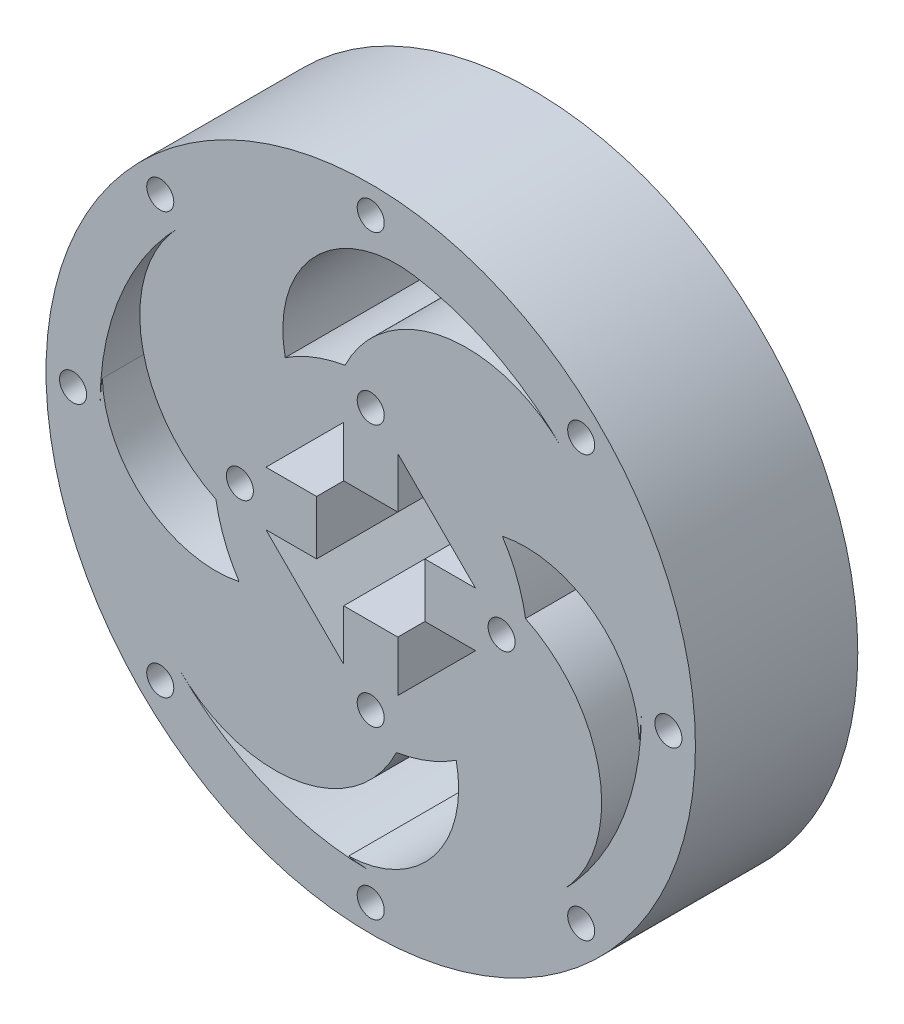
SolidWorks part; units mm, degrees
ref_plane "Front Plane" through (0, 0, 0) normal (0, 0, 1) x (1, 0, 0)
ref_plane "Top Plane" through (0, 0, 0) normal (0, 1, 0) x (1, 0, 0)
ref_plane "Right Plane" through (0, 0, 0) normal (1, 0, 0) x (0, 0, -1)
sketch "Sketch6" plane through (0, 0, 0) normal (0, 0, 1) x (1, 0, 0)
  circle A0 centre (0, 0) radius 20
  circle A1 centre (0, 0) radius 29
  dimension "D1" = 40
  dimension "D2" = 58
extrude "Inner Ring" add sketch "Sketch6" against normal blind 30 separate body
sketch "Sketch7" plane through (0, 0, 0) normal (0, 0, 1) x (1, 0, 0)
  line L2 (-10, 5) -> (-10, -5)
  line L3 (-5, 10) -> (5, 10)
  line L4 (10, 5) -> (10, -5)
  line L5 (-5, -10) -> (5, -10)
  line L14 (-19.3649, 5) -> (-10, 5)
  line L15 (-19.3649, -5) -> (-10, -5)
  line L16 (-5, 19.3649) -> (-5, 10)
  line L17 (5, 19.3649) -> (5, 10)
  line L18 (19.3649, 5) -> (10, 5)
  line L19 (19.3649, -5) -> (10, -5)
  line L20 (5, -19.3649) -> (5, -10)
  line L21 (-5, -19.3649) -> (-5, -10)
  circle A1 centre (0, 0) radius 20
  circle M19 centre (0, 0) radius 20
  dimension "D1" = 20
  dimension "D2" = 20
  dimension "D3" = 10
  dimension "D5" = 10
  dimension "D7" = 10
  dimension "D8" = 10
extrude "Motor Connector Cut" add sketch "Sketch7" against normal blind 30 contours L19 L18 L4 M19 | L17 L16 L3 M19 | L15 L2 L14 M19 | L21 L20 L5 M19 region at (-14.8967, 0, 0) region at (0, 14.8967, 0) region at (0, -14.8967, 0) region at (14.8967, 0, 0)
sketch "Sketch8" plane through (0, 0, 0) normal (0, 0, 1) x (1, 0, 0)
  circle A1 centre (0, 24.1825) radius 2.5
  circle A2 centre (24.1825, 0) radius 2.5
  circle A3 centre (0, -24.1825) radius 2.5
  circle A4 centre (-24.1825, 0) radius 2.5
  dimension "D1" = 5
  dimension "D2" = 5
  dimension "D3" = 5
  dimension "D4" = 5
  dimension "D6" = 48.3649
  dimension "D8" = 48.3649
extrude "M3 Holes" cut sketch "Sketch8" against normal blind 100 and the other way blind 38
sketch "Sketch9" plane through (0, 0, 0) normal (0, 0, 1) x (1, 0, 0)
  circle A0 centre (0, 0) radius 50
  circle A1 centre (0, 0) radius 60
  circle A3 centre (0, 55) radius 2.5
  circle A4 centre (-38.8909, 38.8909) radius 2.5
  circle A5 centre (-55, 0) radius 2.5
  circle A6 centre (-38.8909, -38.8909) radius 2.5
  circle A7 centre (0, -55) radius 2.5
  circle A8 centre (38.8909, -38.8909) radius 2.5
  circle A9 centre (55, 0) radius 2.5
  circle A10 centre (38.8909, 38.8909) radius 2.5
  dimension "D1" = 120
  dimension "D2" = 100
  dimension "D3" = 5
  dimension "D4" = 5
  dimension "D5" = 5
  dimension "D6" = 5
  dimension "D7" = 5
  dimension "D8" = 5
  dimension "D9" = 5
  dimension "D10" = 5
  dimension "D11" = 38.8909
  dimension "D12" = 38.8909
  dimension "D13" = 38.8909
sketch "Sketch10" plane through (0, 0, 0) normal (0, 0, 1) x (1, 0, 0)
  circle A0 centre (0, 0) radius 29
  circle A1 centre (0, 29) radius 21
  circle A2 centre (29, 0) radius 21
  circle A3 centre (0, -29) radius 21
  circle A4 centre (-29, 0) radius 21
  circle A5 centre (0, 0) radius 50
  circle A6 centre (-17.7016, 17.7016) radius 24.9662
  circle A7 centre (17.7016, 17.7016) radius 24.9662
  circle A8 centre (17.7016, -17.7016) radius 24.9662
  circle A9 centre (-17.7016, -17.7016) radius 24.9662
  circle A10 centre (-28.6072, 4.7568) radius 21
  circle A11 centre (-28.6072, -4.7568) radius 21
  circle A12 centre (-4.7568, -28.6072) radius 21
  circle A13 centre (4.7568, -28.6072) radius 21
  circle A14 centre (28.6072, -4.7568) radius 21
  circle A15 centre (28.6072, 4.7568) radius 21
  circle A16 centre (4.7568, 28.6072) radius 21
  circle A17 centre (-4.7568, 28.6072) radius 21
extrude "Middle Pattern" add sketch "Sketch10" against normal blind 30 contours A0 A10 A1 | A16 A6 A1 A10 A0 | A10 A17 A4 A0 A1 | A6 A17 A10 A1 | A1 A17 A6 | A16 A17 A1 A6 | A17 A16 A1 | A16 A5 A1 | A2 A16 A15 A1 A0 | A0 A16 A2 | A16 A0 A14 A7 A2 | A16 A2 A7 A15 | A15 A7 A2 | A14 A15 A2 A7 | A15 A14 A2 | A1 A15 A0 | A2 A13 A0 | A3 A14 A13 A2 A0 | A0 A14 A3 | A14 A0 A12 A8 A3 | A14 A3 A8 A13 | A12 A13 A3 A8 | A3 A13 A8 | A13 A12 A3 | A13 A3 A5 | A15 A2 A5 | A17 A1 A5 | A12 A0 A10 A9 A4 | A4 A12 A11 A3 A0 | A0 A12 A4 | A12 A4 A9 A11 | A4 A11 A9 | A10 A11 A4 A9 | A11 A4 A5 | A11 A10 A4 | A4 A17 A0 | A0 A17 A7 A6 | A17 A0 A15 A1 A7 | A15 A16 A7 A1 | A16 A15 A7 | A15 A5 A7 | A0 A15 A8 A7 | A15 A0 A13 A2 A8 | A13 A14 A8 A2 | A14 A13 A8 | A7 A8 A0 | A6 A7 A0 | A13 A5 A8 | A11 A5 A9 | A12 A11 A9 | A11 A12 A9 A3 | A13 A0 A11 A3 A9 | A0 A13 A9 A8 | A3 A11 A0 | A8 A9 A0 | A17 A4 A6 A11 A0 | A17 A10 A6 A4 | A17 A6 A10 | A0 A11 A6 A9 | A0 A9 A6 | A17 A5 A6 region at (31.1319, 0, 0) region at (33.5178, -9.4084, 0) region at (33.055, 17.4302, 0) region at (33.055, -17.4302, 0) region at (22.797, 19.3194, 0) region at (45.9509, 9.1104, 0) region at (22.797, -19.3194, 0) region at (22.5957, 22.5957, 0) region at (33.6551, 22.0707, 0) region at (45.9267, 13.9422, 0) region at (49.6208, 0, 0) region at (33.6551, -22.0707, 0) region at (22.5957, -22.5957, 0) region at (19.3194, 22.797, 0) region at (31.6778, 31.6778, 0) region at (22.0707, 33.6551, 0) region at (49.7435, 4.1075, 0) region at (19.3194, -22.797, 0) region at (31.6778, -31.6778, 0) region at (22.0707, -33.6551, 0) region at (17.4302, 33.055, 0) region at (43.782, 21.8348, 0) region at (17.4302, -33.055, 0) region at (9.4084, 33.5178, 0) region at (21.8348, -43.782, 0) region at (13.9422, -45.9267, 0) region at (0, 31.1319, 0) region at (4.1075, 49.7435, 0) region at (4.1075, -49.7435, 0) region at (0, -31.1319, 0) region at (9.1104, -45.9509, 0) region at (0, 49.6208, 0) region at (-4.1075, 49.7435, 0) region at (0, -49.6208, 0) region at (-9.4084, -33.5178, 0) region at (-17.4302, 33.055, 0) region at (-9.1104, 45.9509, 0) region at (-13.9422, 45.9267, 0) region at (-21.8348, 43.782, 0) region at (-17.4302, -33.055, 0) region at (-19.3194, 22.797, 0) region at (-22.0707, 33.6551, 0) region at (-31.6778, 31.6778, 0) region at (-22.0707, -33.6551, 0) region at (-43.782, -21.8348, 0) region at (-31.6778, -31.6778, 0) region at (-31.1319, 0, 0) region at (-33.5178, 9.4084, 0) region at (-19.3194, -22.797, 0) region at (-22.5957, 22.5957, 0) region at (-33.6551, 22.0707, 0) region at (-22.5957, -22.5957, 0) region at (-49.7435, -4.1075, 0) region at (-45.9267, -13.9422, 0) region at (-33.6551, -22.0707, 0) region at (-33.055, -17.4302, 0) region at (-33.055, 17.4302, 0) region at (-22.797, 19.3194, 0) region at (-22.797, -19.3194, 0) region at (-49.6208, 0, 0)
extrude "Boss-Extrude1" add sketch "Sketch9" against normal blind 30 separate body
sketch "Sketch11" plane through (0, 0, 0) normal (0, 0, 1) x (1, 0, 0)
  line L0 (-19.3649, 5) -> (-5, 19.3649)
  line L2 (5, 19.3649) -> (19.3649, 5)
  line L4 (19.3649, -5) -> (5, -19.3649)
  line L6 (-5, -19.3649) -> (-19.3649, -5)
  arc A0 (-5, 19.3649) -> (-19.3649, 5) centre (0, 0) ccw
  arc A1 (5, -19.3649) -> (19.3649, -5) centre (0, 0) ccw
  arc A2 (-19.3649, -5) -> (-5, -19.3649) centre (0, 0) ccw
  arc A3 (19.3649, 5) -> (5, 19.3649) centre (0, 0) ccw
extrude "Boss-Extrude2" add sketch "Sketch11" against normal blind 30
